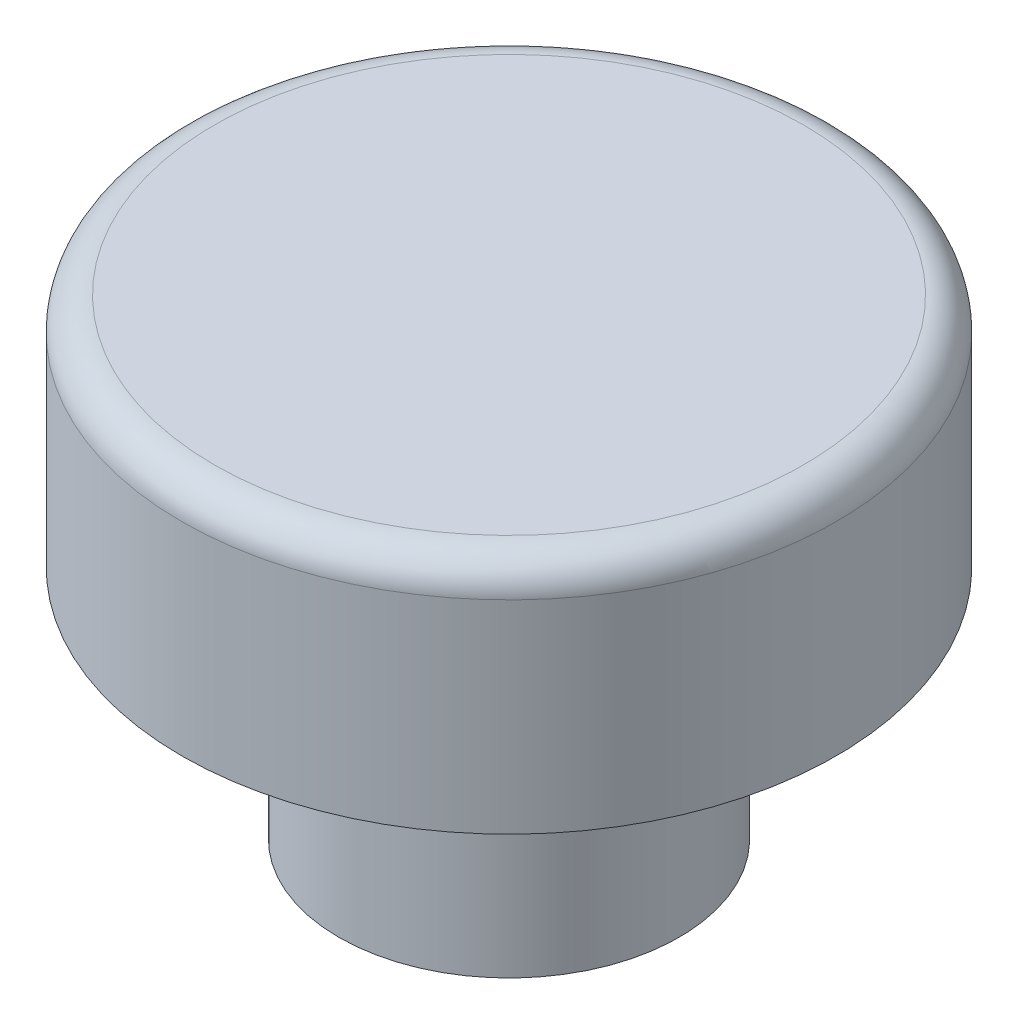
SolidWorks part; units mm, degrees
ref_plane "Front Plane" through (0, 0, 0) normal (0, 0, 1) x (1, 0, 0)
ref_plane "Top Plane" through (0, 0, 0) normal (0, 1, 0) x (1, 0, 0)
ref_plane "Right Plane" through (0, 0, 0) normal (1, 0, 0) x (0, 0, -1)
sketch "Sketch1" plane through (0, 0, 0) normal (0, 1, 0) x (1, 0, 0)
  line L0 (0, -2.05) -> (0, 2.05) construction
  line L1 (-2.05, 0) -> (2.05, 0) construction
  line L2 (-0.585, 0.885) -> (-0.585, 2.05)
  line L3 (-0.585, -2.05) -> (0.585, -2.05)
  line L4 (-0.585, -2.05) -> (-0.585, -0.885)
  line L5 (-0.585, 2.05) -> (0.585, 2.05)
  line L6 (0.585, -2.05) -> (0.585, -0.885)
  line L7 (-0.585, -2.05) -> (0.585, 2.05) construction
  line L8 (-0.585, 2.05) -> (0.585, -2.05) construction
  line L9 (-2.05, -0.585) -> (-0.885, -0.585)
  line L10 (-2.05, -0.585) -> (-2.05, 0.585)
  line L11 (-2.05, 0.585) -> (-0.885, 0.585)
  line L12 (2.05, -0.585) -> (2.05, 0.585)
  line L13 (-2.05, -0.585) -> (2.05, 0.585) construction
  line L14 (-2.05, 0.585) -> (2.05, -0.585) construction
  line L15 (0.885, 0.585) -> (2.05, 0.585)
  line L16 (0.585, 0.885) -> (0.585, 2.05)
  line L17 (0.885, -0.585) -> (2.05, -0.585)
  circle A0 centre (0, 0) radius 2.6
  arc A1 (-0.585, -0.885) -> (-0.885, -0.585) centre (-0.885, -0.885) ccw
  arc A2 (0.585, -0.885) -> (0.885, -0.585) centre (0.885, -0.885) cw
  arc A3 (0.885, 0.585) -> (0.585, 0.885) centre (0.885, 0.885) cw
  arc A4 (-0.585, 0.885) -> (-0.885, 0.585) centre (-0.885, 0.885) cw
  point P5 (0, 0)
  point P8 (0, 0)
  point P20 (2.05, 0)
  point P21 (0, 2.05)
  dimension "D1" = 5.2
  dimension "D4" = 0.3
  dimension "D2" = 4.1
  dimension "D3" = 1.17
extrude "stem housing" add sketch "Sketch1" along normal blind 3.6
sketch "Sketch2" plane through (0, 3.6, 0) normal (0, 1, 0) x (1, 0, 0)
  circle A0 centre (0, 0) radius 5
  dimension "D1" = 10
extrude "button head" add sketch "Sketch2" along normal blind 3.6
fillet "Fillet1" radius 0.5 1 edges at (0, 7.2, 5)
